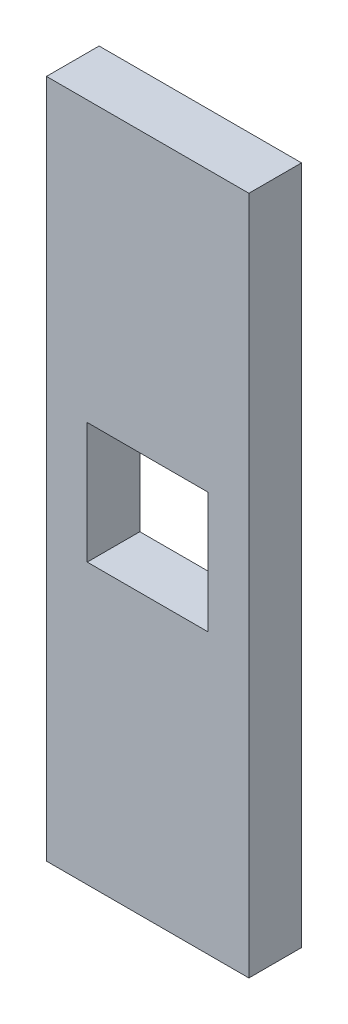
SolidWorks part; units mm, degrees
ref_plane "Front Plane" through (0, 0, 0) normal (0, 0, 1) x (1, 0, 0)
ref_plane "Top Plane" through (0, 0, 0) normal (0, 1, 0) x (1, 0, 0)
ref_plane "Right Plane" through (0, 0, 0) normal (1, 0, 0) x (0, 0, -1)
sketch "Sketch1" plane through (0, 0, 0) normal (0, 0, 1) x (1, 0, 0)
  line L0 (0, 67.15) -> (0, 44.75)
  line L1 (0, 67.15) -> (20, 67.15)
  line L2 (0, 44.75) -> (0, 39.55)
  line L3 (20, 0) -> (0, 0)
  line L4 (4.025, 39.55) -> (15.975, 39.55)
  line L5 (4.025, 27.6) -> (15.975, 27.6)
  line L6 (4.025, 39.55) -> (4.025, 27.6)
  line L7 (15.975, 39.55) -> (15.975, 27.6)
  line L8 (0, 44.75) -> (20, 44.75) construction
  line L9 (0, 39.55) -> (20, 39.55) construction
  line L10 (0, 39.55) -> (0, 27.6)
  line L11 (0, 27.6) -> (0, 22.4)
  line L12 (20, 44.75) -> (20, 39.55)
  line L13 (20, 67.15) -> (20, 44.75)
  line L14 (0, 22.4) -> (0, 0)
  line L15 (20, 39.55) -> (20, 27.6)
  line L16 (20, 27.6) -> (20, 22.4)
  line L17 (20, 22.4) -> (20, 0)
  line L18 (0, 27.6) -> (20, 27.6) construction
  line L19 (20, 22.4) -> (0, 22.4) construction
  line L20 (10, -0.0005) -> (10, 4.0956) construction
  point P18 (10, 27.6)
  point P20 (10, 39.55)
  point P21 (10, 67.15)
  dimension "D1" = 22.4
  dimension "D2" = 11.95
  dimension "D3" = 5.2
  dimension "D4" = 20
  dimension "D5" = 11.95
  dimension "D6" = 11.95
extrude "Boss-Extrude1" add sketch "Sketch1" along normal blind 5.2
